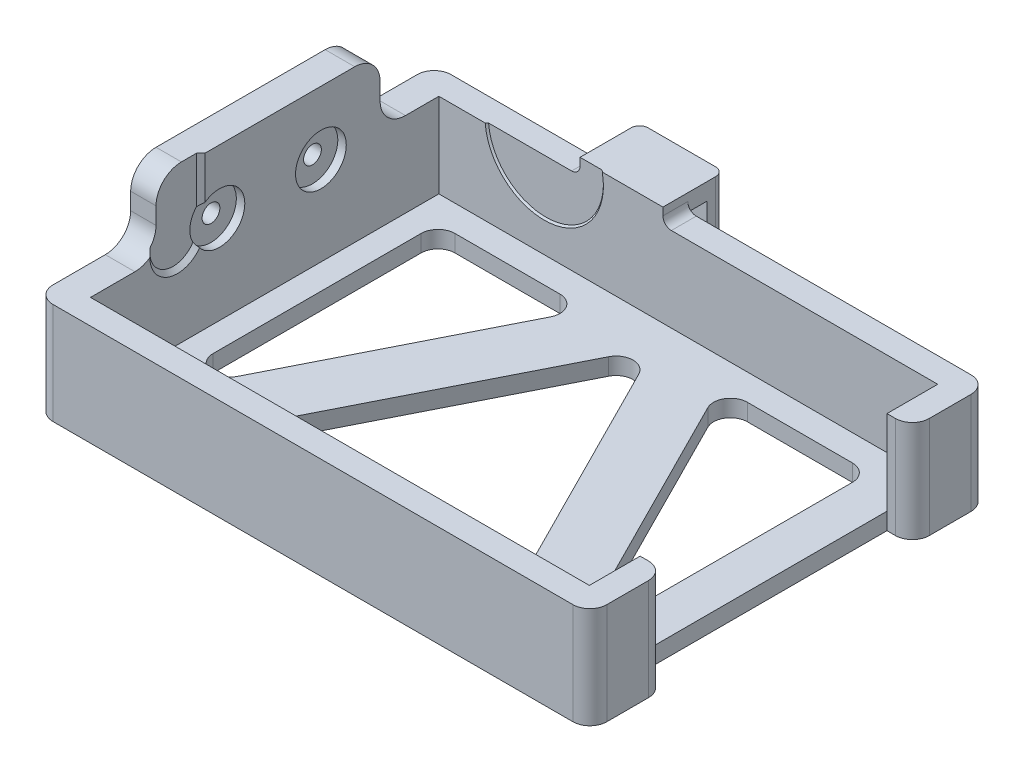
SolidWorks part; units mm, degrees
material "ABS"
ref_plane "Front Plane" through (0, 0, 0) normal (0, 0, 1) x (1, 0, 0)
ref_plane "Top Plane" through (0, 0, 0) normal (0, 1, 0) x (1, 0, 0)
ref_plane "Right Plane" through (0, 0, 0) normal (1, 0, 0) x (0, 0, -1)
sketch "Sketch1" plane through (0, 0, 0) normal (0, 1, 0) x (1, 0, 0)
  line L0 (0, 20.5) -> (65.9167, 20.5) construction
  line L1 (0, 0) -> (50.0896, 0) construction
  line L2 (0, 23.54) -> (0, -23.54)
  line L3 (0, -23.54) -> (65.5, -23.54)
  line L4 (3.5, 28) -> (3.5, -29.0344) construction
  line L8 (65.5, -23.54) -> (65.5, 23.54)
  line L9 (65.5, 23.54) -> (0, 23.54)
  dimension "D1" = 20.5
  dimension "D2" = 3.04
  dimension "D3" = 62
  dimension "D4" = 3.5
extrude "Boss-Extrude1" add sketch "Sketch1" along normal blind 2
sketch "Sketch2" plane through (0, 2, 0) normal (0, 1, 0) x (1, 0, 0)
  line L0 (62.5, 20.6) -> (3.5, 20.6)
  line L1 (3.5, 20.6) -> (3.5, -20.6)
  line L2 (3.5, -20.6) -> (62.5, -20.6)
  line L3 (0, 0) -> (15.6663, 0) construction
  line L5 (62.5, 20.6) -> (62.5, 14.6)
  line L6 (62.5, 14.6) -> (65.5, 14.6)
  line L7 (62.5, -14.6) -> (65.5, -14.6)
  line L8 (0, 23.54) -> (0, -23.54)
  line L9 (0, -23.54) -> (65.5, -23.54)
  line L10 (62.5, -20.6) -> (62.5, -14.6)
  line L15 (65.5, 23.54) -> (0, 23.54)
  line L16 (0, 23.54) -> (0, -23.54)
  line L17 (0, -23.54) -> (65.5, -23.54)
  line L23 (65.5, 23.54) -> (0, 23.54)
  line L26 (65.5, -23.54) -> (65.5, 23.54)
  line L27 (65.5, -23.54) -> (65.5, 23.54)
  line M17 (0, 23.54) -> (0, -23.54)
  line M19 (0, -23.54) -> (65.5, -23.54)
  line M29 (65.5, -23.54) -> (65.5, 23.54)
  line M31 (65.5, 23.54) -> (0, 23.54)
  dimension "D2" = 41.2
  dimension "D3" = 3.5
  dimension "D4" = 6
  dimension "D5" = 59
  dimension "D1" = 0
extrude "Boss-Extrude2" add sketch "Sketch2" along normal blind 10 contours L3 L1 L0 M17 M29 M31 | L3 L16 L2 L1 M19 region at (33, 2, -21.296) region at (2.804, 2, 10.3)
ref_plane "Plane1" through (0, 12.5, 0) normal (0, -1, 0) x (-1, 0, 0)
sketch "Sketch3" plane through (0, 0, 0) normal (-1, 0, 0) x (0, 0, 1)
  line L0 (-23.54, 12) -> (23.54, 12) construction
  line L1 (-23.54, 12) -> (-16.65, 12)
  line L2 (-0.65, -6.3525) -> (-0.65, 20.1937) construction
  line L3 (-23.54, 12) -> (23.54, 12) construction
  line L4 (-13.65, 15) -> (-13.65, 17)
  line L5 (-10.65, 20) -> (9.35, 20)
  line L6 (12.35, 17) -> (12.35, 15)
  line L7 (-23.54, 12) -> (-16.65, 12)
  line L8 (15.35, 12) -> (23.54, 12)
  line L9 (-16.65, 12) -> (15.35, 12)
  arc A0 (12.35, 17) -> (9.35, 20) centre (9.35, 17) ccw
  arc A1 (-10.65, 20) -> (-13.65, 17) centre (-10.65, 17) ccw
  arc A2 (-13.65, 15) -> (-16.65, 12) centre (-16.65, 15) cw
  arc A3 (15.35, 12) -> (12.35, 15) centre (15.35, 15) cw
  point P16 (12.35, 12)
  line M3 (23.54, 12) -> (-23.54, 12)
  dimension "D1" = 0.65
  dimension "D4" = 3
  dimension "D2" = 26
  dimension "D3" = 8
extrude "Boss-Extrude3" add sketch "Sketch3" against normal up to surface (3.5 mm away) contours L9 L2 L5 A1 L4 A2 | L2 A3 L6 A0 L5 M3 region at (0, 15.8763, -7.1749) region at (0, 15.8763, 5.8749) up to face at (3.5, 7, 0)
sketch "Sketch4" plane through (0, 0, 0) normal (-1, 0, 0) x (0, 0, 1)
  line L0 (-0.65, 20) -> (-0.65, 5.0688) construction
  line L7 (-29.7, 12.5) -> (29.7, 12.5) construction
  line L9 (-10.65, 20) -> (9.35, 20) construction
  circle A2 centre (-6.65, 12.5) radius 1.05
  circle A3 centre (5.35, 12.5) radius 1.05
  dimension "D1" = 2.1
  dimension "D2" = 12
extrude "Cut-Extrude1" cut sketch "Sketch4" against normal through all contours A2 | A3 region at (0, 12.5, -6.65) region at (0, 12.5, 5.35)
ref_axis "Axis1" through (0, 12.5, -6.65) along (-1, 0, 0)
ref_axis "Axis2" through (1.9366, 12.5, 5.35) along (-1, 0, 0)
sketch "Sketch6" plane through (0, 2, 0) normal (0, 1, 0) x (1, 0, 0)
  line L0 (6.5, 15.5) -> (6.5, -9.0963)
  line L1 (10.2856, -9.9972) -> (22.6958, 14.5991)
  line L2 (20.9102, 17.5) -> (8.5, 17.5)
  line L3 (15.8042, -14.5991) -> (30.2144, 13.9611)
  line L4 (65.5, -14.6) -> (65.5, 14.6)
  line L5 (62.5, 20.6) -> (3.5, 20.6)
  line L6 (3.5, 20.6) -> (3.5, -20.6)
  line L7 (3.5, -20.6) -> (62.5, -20.6)
  line L8 (65.5, -14.6) -> (65.5, 14.6)
  line L9 (62.5, 20.6) -> (3.5, 20.6)
  line L10 (3.5, 20.6) -> (3.5, -20.6)
  line L11 (3.5, -20.6) -> (62.5, -20.6)
  line L12 (33.7856, 13.9611) -> (48.1958, -14.5991)
  line L13 (46.4102, -17.5) -> (17.5898, -17.5)
  line L15 (57.5, -9.0963) -> (57.5, 15.5)
  line L16 (55.5, 17.5) -> (43.0898, 17.5)
  line L17 (41.3042, 14.5991) -> (53.7144, -9.9972)
  line L18 (0, 0) -> (50.9024, 0) construction
  line L26 (65.5, 14.6) -> (62.5, 14.6)
  line L27 (65.5, 14.6) -> (62.5, 14.6)
  line L28 (62.5, 14.6) -> (62.5, 20.6)
  line L29 (62.5, 14.6) -> (62.5, 20.6)
  line L30 (62.5, -20.6) -> (62.5, -14.6)
  line L31 (62.5, -20.6) -> (62.5, -14.6)
  line L32 (62.5, -14.6) -> (65.5, -14.6)
  line L33 (62.5, -14.6) -> (65.5, -14.6)
  arc A0 (43.0898, 17.5) -> (41.3042, 14.5991) centre (43.0898, 15.5) ccw
  arc A1 (57.5, 15.5) -> (55.5, 17.5) centre (55.5, 15.5) ccw
  arc A6 (48.1958, -14.5991) -> (46.4102, -17.5) centre (46.4102, -15.5) cw
  arc A7 (57.5, -9.0963) -> (53.7144, -9.9972) centre (55.5, -9.0963) cw
  arc A8 (30.2144, 13.9611) -> (33.7856, 13.9611) centre (32, 13.0601) cw
  arc A9 (22.6958, 14.5991) -> (20.9102, 17.5) centre (20.9102, 15.5) ccw
  arc A10 (15.8042, -14.5991) -> (17.5898, -17.5) centre (17.5898, -15.5) ccw
  arc A11 (6.5, -9.0963) -> (10.2856, -9.9972) centre (8.5, -9.0963) ccw
  arc A12 (6.5, 15.5) -> (8.5, 17.5) centre (8.5, 15.5) cw
  point P29 (57.5, -17.5)
  point P32 (32, 17.5)
  point P40 (6.5, -17.5)
  point P43 (6.5, 17.5)
  dimension "D7" = 2
  dimension "D2" = 7
  dimension "D3" = 7
  dimension "D4" = 5
  dimension "D5" = 35
  dimension "D6" = 3
  dimension "D1" = 0
extrude "Cut-Extrude3" cut sketch "Sketch6" against normal through all contours L0 L18 L1 L2 | L18 L0 L1 | L3 L18 L12 | L18 L3 L13 L12 | L18 L17 L15 | L15 A1 L16 A0 L17 A7 region at (13.2894, 2, -9.6197) region at (51.4978, 2, -6.4431) region at (32, 2, -5.6032) region at (32, 2, 9.6475) region at (9.7687, 2, 4.588)
ref_plane "Plane2" through (0, 12.5, 0) normal (0, 1, 0) x (1, 0, 0)
ref_plane "Plane3" through (28.5, 0, 0) normal (1, 0, 0) x (0, 0, -1)
ref_plane "Plane4" through (0, 0, 0) normal (0, 0, 1) x (1, 0, 0)
sketch "Sketch23" plane through (3.5, 0, 0) normal (1, 0, 0) x (0, 0, -1)
  line L0 (-13.5745, 12.541) -> (-13.5745, 22.9975)
  line L1 (-13.5745, 22.9975) -> (-7.0745, 22.9975)
  line L2 (-7.0745, 22.9975) -> (-7.0745, 12.541)
  arc A0 (-13.5745, 12.541) -> (-7.0745, 12.541) centre (-10.3245, 12.541) ccw
  circle A2 centre (-10.3245, 12.541) radius 3.0099 construction
  dimension "D1" = 6.5
extrude "Cut-Extrude8" cut sketch "Sketch23" against normal blind 0.5 draft 45
sketch "Sketch25" plane through (0, 2, 0) normal (0, 1, 0) x (1, 0, 0)
  line L1 (62.5, 14.6) -> (65.5, 14.6)
  line L2 (62.5, 14.6) -> (62.5, -14.6)
  line L3 (62.5, -14.6) -> (65.5, -14.6)
  line L4 (65.5, 14.6) -> (65.5, -14.6)
extrude "Cut-Extrude10" cut sketch "Sketch25" against normal through all
fillet "Fillet1" radius 2 6 edges at (0, 6, 23.54) (0, 6, -23.54) (65.5, 6, -23.54) (65.5, 6, 23.54)
ref_plane "Plane5" through (20, 0, 0) normal (-1, 0, 0) x (0, 0, 1)
sketch "Sketch26" plane through (20, 0, 0) normal (-1, 0, 0) x (0, 0, 1)
  line L0 (-23.54, 0) -> (-23.54, 12)
  line L1 (-23.54, 0) -> (-23.54, 2)
  line L2 (-23.54, 0) -> (-27.84, 0)
  line L3 (-27.84, 0) -> (-27.84, 12)
  line L5 (-25.84, 2) -> (-23.54, 2)
  line L6 (-25.84, 2) -> (-25.84, 11.9)
  line L7 (-25.84, 11.9) -> (-23.54, 11.9)
  line L8 (-23.54, 11.9) -> (-23.54, 12)
  line L9 (-20.6, 12) -> (-20.6, 2) construction
  line L10 (-20.6, 12) -> (-23.54, 12)
  line L11 (-20.6, 12) -> (-20.6, 13.9)
  line L12 (-20.6, 13.9) -> (-27.84, 13.9)
  line L13 (-27.84, 12) -> (-27.84, 13.9)
  line L14 (-20.6, 12) -> (-20.6, 2) construction
  dimension "D1" = 9.9
  dimension "D2" = 2
  dimension "D3" = 2
  dimension "D4" = 2
  dimension "D5" = 2.3
extrude "Boss-Extrude4" add sketch "Sketch26" against normal blind 10 contours L6 L7 L1 L3 L2 L5 region at (20, 0.1567, -25.69)
fillet "Fillet2" radius 1 4 edges at (20, 6.95, -27.84) (20, 1, -23.54) (30, 6.95, -27.84) (30, 1, -23.54)
sketch "Sketch27" plane through (3.5, 0, 0) normal (1, 0, 0) x (0, 0, -1)
  circle A0 centre (-5.35, 12.5) radius 3
  circle A1 centre (6.65, 12.5) radius 3
  dimension "D1" = 6
extrude "Cut-Extrude11" cut sketch "Sketch27" against normal blind 1
fillet "Fillet4" radius 1 2 edges at (20, 12, -22.07) (30, 12, -22.07)
sketch "Sketch24" plane through (0, 0, -20.6) normal (0, 0, 1) x (1, 0, 0)
  circle A0 centre (15.9587, 12.541) radius 7
  dimension "D1" = 14
extrude "Cut-Extrude9" cut sketch "Sketch24" against normal blind 0.2 draft 45
mirror "Mirror1" [suppressed] about plane through (0, 0, 0) normal (0, 0, 1)
fillet "Fillet5" [suppressed] radius 1
equation "\"D3@Sketch6\"=\"D2@Sketch6\""
